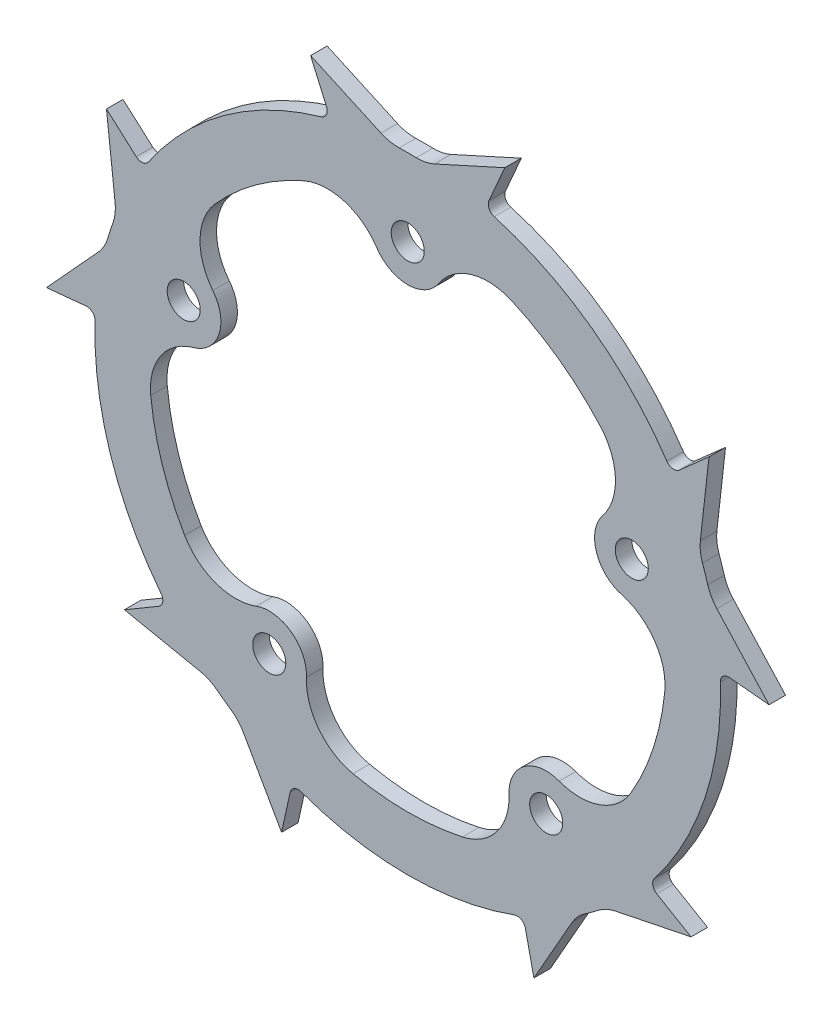
SolidWorks part; units mm, degrees
material "Alloy Steel (SS)"
ref_plane "Front Plane" through (0, 0, 0) normal (0, 0, 1) x (1, 0, 0)
ref_plane "Top Plane" through (0, 0, 0) normal (0, 1, 0) x (1, 0, 0)
ref_plane "Right Plane" through (0, 0, 0) normal (1, 0, 0) x (0, 0, -1)
sketch "Sketch1" plane through (0, 0, 0) normal (0, 0, 1) x (1, 0, 0)
  line L0 (0, 0) -> (0, 28.956) construction
  line L1 (0, 0) -> (27.5388, 8.9479) construction
  line L2 (0, 0) -> (17.0199, -23.4259) construction
  line L3 (0, 0) -> (-17.0199, -23.4259) construction
  line L4 (0, 0) -> (-27.5388, 8.9479) construction
  line L5 (-9.5106, 37.2552) -> (-11.938, 42.8169)
  line L6 (-11.938, 42.8169) -> (0, 0) construction
  line L7 (-11.938, 42.8169) -> (-3.2859, 38.8883)
  line L8 (0, 0) -> (0, 44.45) construction
  line L9 (9.5106, 37.2552) -> (11.938, 42.8169)
  line L10 (11.938, 42.8169) -> (3.2859, 38.8883)
  line L11 (-10.3266, 37.0373) -> (13.7805, 43.7588) construction
  line L12 (-11.938, 42.8169) -> (-5.2343, 44.686) construction
  circle A0 centre (0, 0) radius 44.45 construction
  circle A1 centre (0, 0) radius 31.75
  circle A2 centre (0, 28.956) radius 2.032
  arc A3 (3.81, 26.4287) -> (-3.81, 26.4287) centre (0, 28.956) cw
  arc A4 (3.81, 26.4287) -> (12.7862, 29.0616) centre (9.8617, 22.4145) cw
  arc A5 (-3.81, 26.4287) -> (-12.7862, 29.0616) centre (-9.8617, 22.4145) ccw
  arc A6 (23.9579, 11.7905) -> (23.6881, 21.1409) centre (18.2701, 16.3055) ccw
  arc A7 (26.3126, 4.5434) -> (23.9579, 11.7905) centre (27.5388, 8.9479) cw
  circle A8 centre (27.5388, 8.9479) radius 2.032
  arc A9 (26.3126, 4.5434) -> (31.5904, -3.1798) centre (24.3649, -2.4525) cw
  arc A10 (18.6168, -19.1418) -> (27.4262, -15.9958) centre (21.1532, -12.3372) ccw
  arc A11 (12.4521, -23.6208) -> (18.6168, -19.1418) centre (17.0199, -23.4259) cw
  circle A12 centre (17.0199, -23.4259) radius 2.032
  arc A13 (12.4521, -23.6208) -> (6.7378, -31.0268) centre (5.1967, -23.9303) cw
  arc A14 (-12.4521, -23.6208) -> (-6.7378, -31.0268) centre (-5.1967, -23.9303) ccw
  arc A15 (-18.6168, -19.1418) -> (-12.4521, -23.6208) centre (-17.0199, -23.4259) cw
  circle A16 centre (-17.0199, -23.4259) radius 2.032
  arc A17 (-18.6168, -19.1418) -> (-27.4262, -15.9958) centre (-21.1532, -12.3372) cw
  arc A18 (-26.3126, 4.5434) -> (-31.5904, -3.1798) centre (-24.3649, -2.4525) ccw
  arc A19 (-23.9579, 11.7905) -> (-26.3126, 4.5434) centre (-27.5388, 8.9479) cw
  circle A20 centre (-27.5388, 8.9479) radius 2.032
  arc A21 (-23.9579, 11.7905) -> (-23.6881, 21.1409) centre (-18.2701, 16.3055) cw
  circle A22 centre (0, 0) radius 38.45
  arc A23 (-3.2859, 38.8883) -> (-1.0473, 38.4357) centre (-1.1856, 43.5139) ccw
  arc A24 (3.2859, 38.8883) -> (1.0473, 38.4357) centre (1.1856, 43.5139) cw
  point P47 (0, 0)
  dimension "D1" = 88.9
  dimension "D2" = 63.5
  dimension "D3" = 4.064
  dimension "D4" = 28.956
  dimension "D6" = 2.54
  dimension "D8" = 6
  dimension "D12" = 5.08
  dimension "D10" = 40
  dimension "D7" = 7.62
  dimension "D9" = 8
  dimension "D11" = 23.876
  dimension "D5" = 5
extrude "Boss-Extrude1" add sketch "Sketch1" along normal blind 2.032 contours A0 A1 | A19 A21 A1 A18 A20 | A5 A3 A4 A1 A2 | A7 A9 A1 A6 A8 | A11 A13 A1 A10 A12 | A15 A17 A1 A14 A16 region at (-5.1616, 37.0042, 0) region at (31.6842, -1.5906, 0) region at (7.7428, 29.6383, 0) region at (18.5119, -25.4794, 0) region at (-25.7875, 16.5223, 0) region at (-18.5119, -25.4794, 0)
extrude "Boss-Extrude5" add sketch "Sketch1<5>" along normal up to surface (2.032 mm away) contours L7 L5 A22 | A22 L9 L10 region at (-7.9331, 39.5489, 0) region at (7.9331, 39.5489, 0) up to face at (0, 0, 2.032)
sketch "Sketch1<5>" plane through (0, 0, 0) normal (0, 0, 1) x (1, 0, 0) same geometry as "Sketch1"
fillet "Fillet2" radius 1.016 2 edges at (9.5106, 37.2552, 1.016) (-9.5106, 37.2552, 1.016)
pattern_circular "CirPattern2" count 5 over 360 about axis through (0, 0, 2.032) along (0, 0, 1) of "Boss-Extrude5", "Fillet2"
